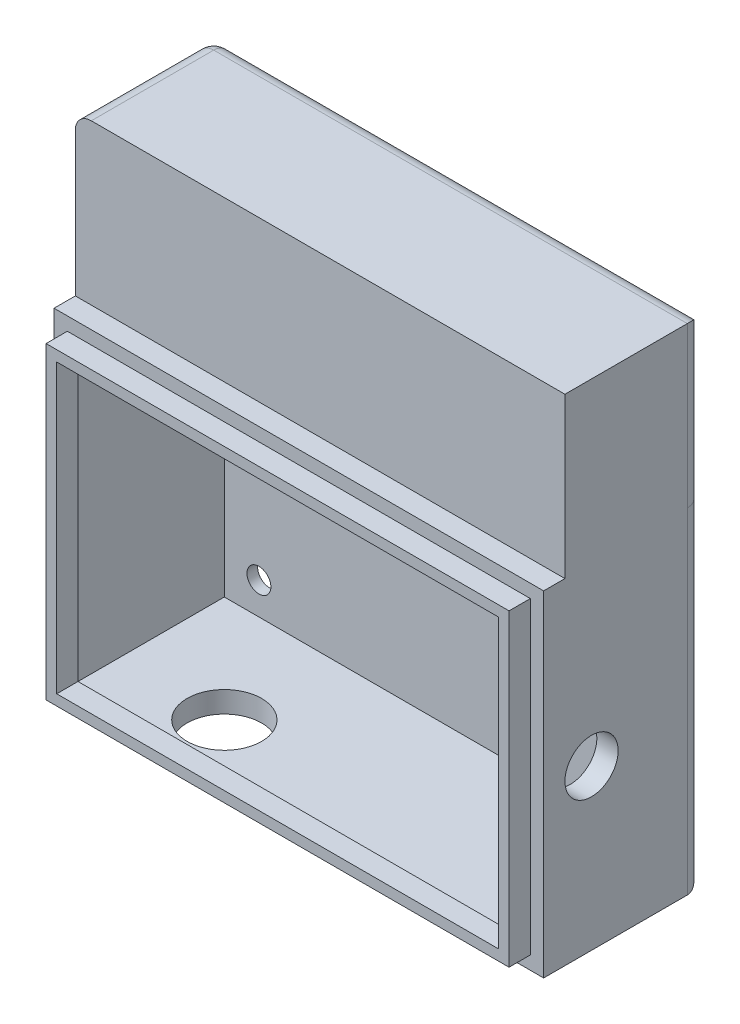
SolidWorks part; units mm, degrees
ref_plane "Front Plane" through (0, 0, 0) normal (0, 0, 1) x (1, 0, 0)
ref_plane "Top Plane" through (0, 0, 0) normal (0, 1, 0) x (1, 0, 0)
ref_plane "Right Plane" through (0, 0, 0) normal (1, 0, 0) x (0, 0, -1)
sketch "Sketch3" plane through (0, 0, 0) normal (0, 0, 1) x (1, 0, 0)
  line L1 (0, 0) -> (92, 0)
  line L2 (0, 0) -> (0, 63)
  line L3 (0, 63) -> (92, 63)
  line L4 (92, 0) -> (92, 63)
  line L5 (8, 55.5) -> (84.5, 55.5)
  line L6 (8, 55.5) -> (8, 7.5)
  line L7 (8, 7.5) -> (84.5, 7.5)
  line L8 (84.5, 55.5) -> (84.5, 7.5)
  circle A4 centre (82, 53) radius 2.25
  circle A5 centre (82, 10) radius 2.25
  circle A6 centre (10.5, 10) radius 2.25
  circle A7 centre (10.5, 53) radius 2.25
  dimension "D23" = 4.5
  dimension "D24" = 4.5
  dimension "D25" = 4.5
  dimension "D26" = 4.5
  dimension "D1" = 63
  dimension "D2" = 92
  dimension "D3" = 48
  dimension "D4" = 76.5
  dimension "D5" = 7.5
  dimension "D6" = 8
  dimension "D8" = 7.5
  dimension "D27" = 2.5
  dimension "D28" = 2.5
  dimension "D29" = 2.5
  dimension "D30" = 2.5
  dimension "D31" = 2.5
  dimension "D32" = 2.5
  dimension "D33" = 2.5
  dimension "D34" = 2.5
extrude "Boss-Extrude3" add sketch "Sketch3" along normal blind 30 contours L8 L5 L6 L7 A7 A6 A5 A4 | L1 L4 L3 L2 L5 L8 L7 L6 region at (1.115, 31.5, 0) region at (46.25, 31.5, 0)
sketch "Sketch4" plane through (0, 0, 30) normal (0, 0, 1) x (1, 0, 0)
  line L0 (0, 0) -> (0, 63) construction
  line L1 (4, 59) -> (88, 59)
  line L2 (4, 59) -> (4, 4)
  line L3 (4, 4) -> (88, 4)
  line L4 (88, 59) -> (88, 4)
  line L5 (0, 0) -> (92, 0) construction
  line L6 (0, 63) -> (92, 63) construction
  line L7 (92, 0) -> (92, 63) construction
  dimension "D1" = 4
  dimension "D2" = 4
  dimension "D3" = 4
  dimension "D4" = 4
extrude "Cut-Extrude1" cut sketch "Sketch4" against normal blind 28
sketch "Sketch5" plane through (0, 0, 30) normal (0, 0, 1) x (1, 0, 0)
  line L0 (0, 0) -> (0, 63) construction
  line L1 (2.5, 60.5) -> (89.5, 60.5)
  line L2 (2.5, 60.5) -> (2.5, 2.5)
  line L3 (2.5, 2.5) -> (89.5, 2.5)
  line L4 (89.5, 60.5) -> (89.5, 2.5)
  line L5 (0, 63) -> (92, 63) construction
  line L6 (92, 0) -> (92, 63) construction
  line L7 (0, 0) -> (92, 0) construction
  dimension "D1" = 2.5
  dimension "D2" = 2.5
  dimension "D3" = 2.5
  dimension "D4" = 2.5
fillet "Fillet1" radius 3 3 edges at (46, 0, 0) (0, 31.5, 0) (92, 31.5, 0)
sketch "Sketch6" plane through (0, 0, 0) normal (-1, 0, 0) x (0, 0, 1)
  line L0 (30, 0) -> (3, 0) construction
  line L1 (27, 18) -> (12, 18)
  line L2 (27, 18) -> (27, 39)
  line L3 (27, 39) -> (12, 39)
  line L4 (12, 18) -> (12, 39)
  line L5 (30, 0) -> (30, 63) construction
  dimension "D1" = 18
  dimension "D2" = 21
  dimension "D3" = 15
  dimension "D4" = 3
extrude "Boss-Extrude4" add sketch "Sketch5" along normal blind 4
sketch "Sketch7" plane through (0, 0, 34) normal (0, 0, 1) x (1, 0, 0)
  line L0 (89.5, 2.5) -> (89.5, 60.5) construction
  line L1 (4.5, 4.5) -> (87.5, 4.5)
  line L2 (4.5, 4.5) -> (4.5, 58.5)
  line L3 (4.5, 58.5) -> (87.5, 58.5)
  line L4 (87.5, 4.5) -> (87.5, 58.5)
  line L5 (89.5, 60.5) -> (2.5, 60.5) construction
  line L6 (2.5, 2.5) -> (89.5, 2.5) construction
  line L7 (2.5, 60.5) -> (2.5, 2.5) construction
  dimension "D1" = 2
  dimension "D2" = 2
  dimension "D3" = 2
  dimension "D4" = 2
extrude "Cut-Extrude4" cut sketch "Sketch7" against normal blind 27
sketch "Sketch9" plane through (0, 0, 0) normal (0, -1, 0) x (1, 0, 0)
  line L0 (0, 30) -> (92, 30) construction
  line L1 (0, 30) -> (0, 3) construction
  circle A0 centre (24, 22) radius 7
  dimension "D1" = 14
  dimension "D2" = 8
  dimension "D3" = 24
extrude "Cut-Extrude6" cut sketch "Sketch9" against normal blind 27
sketch "Sketch11" plane through (92, 0, 0) normal (1, 0, 0) x (0, 0, -1)
  line L0 (-30, 0) -> (-3, 0) construction
  line L1 (-30, 0) -> (-30, 63) construction
  circle A0 centre (-21, 30) radius 5
  dimension "D1" = 10
  dimension "D2" = 30
  dimension "D3" = 9
extrude "Cut-Extrude7" cut sketch "Sketch11" against normal blind 27
sketch "Sketch12" plane through (0, 0, 0) normal (-1, 0, 0) x (0, 0, 1)
  line L0 (30, 0) -> (3, 0) construction
  line L1 (16, 44) -> (16.5, 44)
  line L2 (16, 44) -> (16, 0)
  line L3 (16, 0) -> (16.5, 0)
  line L4 (16.5, 44) -> (16.5, 0)
  line L5 (0, 3) -> (0, 63) construction
  circle A0 centre (16, 44) radius 2.25
  dimension "D1" = 4.5
  dimension "D2" = 44
  dimension "D3" = 16
extrude "Cut-Extrude8" cut sketch "Sketch12" against normal blind 10 contours A0
sketch "Sketch13" plane through (0, 63, 0) normal (0, 1, 0) x (1, 0, 0)
  line L0 (92, -30) -> (92, -3) construction
  line L1 (0, 0) -> (92, 0)
  line L2 (0, 0) -> (0, -26)
  line L3 (0, -26) -> (92, -26)
  line L4 (92, 0) -> (92, -26)
  dimension "D1" = 26
extrude "Boss-Extrude6" add sketch "Sketch13" along normal blind 30
sketch "Sketch14" plane through (0, 0, 0) normal (-1, 0, 0) x (0, 0, 1)
  line L0 (0, 93) -> (0, 63) construction
  line L1 (24.5, 91) -> (1.5, 91)
  line L2 (24.5, 91) -> (24.5, 67)
  line L3 (24.5, 67) -> (1.5, 67)
  line L4 (1.5, 91) -> (1.5, 67)
  line L5 (0, 93) -> (26, 93) construction
  dimension "D1" = 24
  dimension "D2" = 23
  dimension "D3" = 1.5
  dimension "D4" = 2
extrude "Cut-Extrude9" cut sketch "Sketch14" against normal blind 90
fillet "Fillet3" radius 3 2 edges at (46, 93, 0) (92, 78, 0)
fillet "Fillet4" radius 3 2 edges at (0, 93, 14.5) (0, 76.5, 0)
